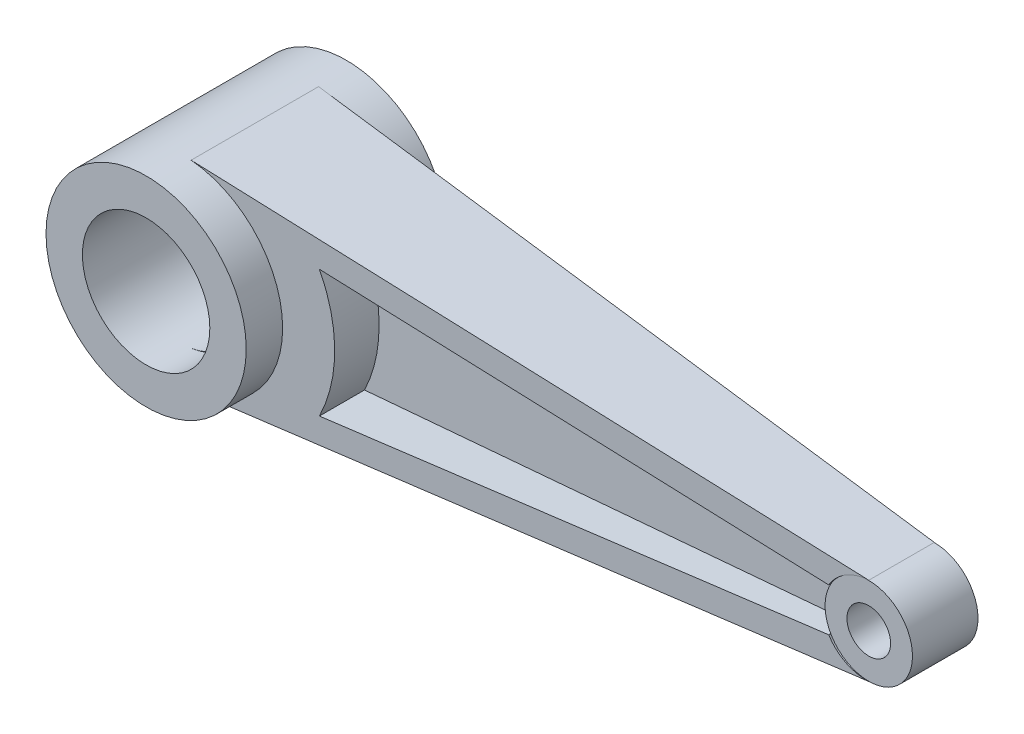
SolidWorks part; units mm, degrees
ref_plane "Front Plane" through (0, 0, 0) normal (0, 0, 1) x (1, 0, 0)
ref_plane "Top Plane" through (0, 0, 0) normal (0, 1, 0) x (1, 0, 0)
ref_plane "Right Plane" through (0, 0, 0) normal (1, 0, 0) x (0, 0, -1)
sketch "Sketch1" plane through (0, 0, 0) normal (0, 0, 1) x (1, 0, 0)
  circle A0 centre (0, 0) radius 27.5
  circle A1 centre (0, 0) radius 17.5
  dimension "D1" = 35
  dimension "D2" = 55
extrude "Boss-Extrude2" add sketch "Sketch1" along normal mid plane 55
sketch "Sketch2" plane through (0, 0, 0) normal (0, 0, 1) x (1, 0, 0)
  line L0 (0, 0) -> (180, 0) construction
  circle A0 centre (180, 0) radius 6
  circle A1 centre (180, 0) radius 12
  dimension "D2" = 12
  dimension "D3" = 24
  dimension "D1" = 180
extrude "Boss-Extrude3" add sketch "Sketch2" along normal mid plane 18 separate body
sketch "Sketch5" plane through (0, 0, 0) normal (0, 0, 1) x (1, 0, 0)
  line L0 (2.3681, 27.3979) -> (180, 12.0447)
  line L1 (0, 0) -> (180, 0) construction
  line L2 (0, -27.5) -> (180, -12.0447)
  line L3 (35.9852, 17.4662) -> (169.5133, 5.925)
  line L4 (35.9852, -17.4662) -> (169.5133, -5.925)
  circle A0 centre (0, 0) radius 27.5 construction
  circle A1 centre (180, 0) radius 12 construction
  arc A2 (2.3681, 27.3979) -> (0, -27.5) centre (0, 0) cw
  arc A3 (180, 12.0447) -> (180, -12.0447) centre (180, 0) ccw
  arc A4 (35.9852, 17.4662) -> (35.9852, -17.4662) centre (0, 0) cw
  arc A5 (169.5133, 5.925) -> (169.5197, -5.9362) centre (180, 0) ccw
  point P13 (0, 0)
  point P14 (0, 0)
  point P18 (0, 0)
  dimension "D1" = 40
  dimension "D2" = 7
extrude "Boss-Extrude4" add sketch "Sketch5" along normal mid plane 35 contours A2 L1 A4 L3 A3 L0 | L1 A2 L2 A3 L4 A4 region at (82.6831, 14.8797, 0) region at (82.815, -14.8319, 0)
extrude "Boss-Extrude5" add sketch "Sketch5<3>" along normal mid plane 7 contours A4 L1 A3 L3 | L1 A4 L4 A5 region at (93.1466, 6.3306, 0) region at (93.1466, -6.3306, 0)
sketch "Sketch5<3>" plane through (0, 0, 0) normal (0, 0, 1) x (1, 0, 0) same geometry as "Sketch5"
sketch "Sketch8" plane through (0, 0, 0) normal (0, 1, 0) x (1, 0, 0)
  line L0 (2.3681, 17.5) -> (180, 9)
  line L1 (192, 9) -> (168, 9) construction
  line L2 (180, 9) -> (180, 17.5)
  line L3 (180, 17.5) -> (2.3681, 17.5)
  line L4 (0, 0) -> (201.3399, 0) construction
  line L5 (180, -9) -> (180, -17.5)
  line L6 (2.3681, -17.5) -> (180, -9)
  line L7 (180, -17.5) -> (2.3681, -17.5)
extrude "Cut-Extrude2" cut sketch "Sketch8" against normal through all both and the other way through all contours L3 L0 L2 | L5 L7 L6
